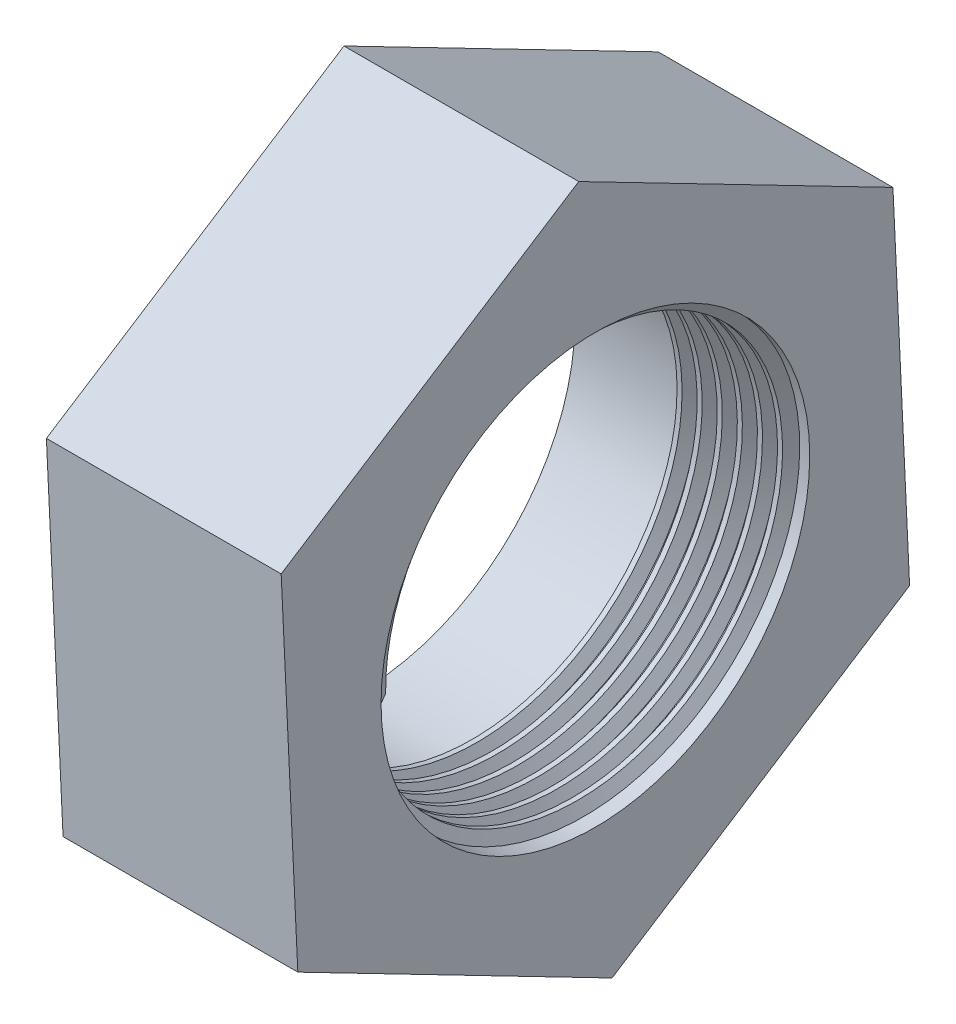
SolidWorks part; units mm, degrees
material "1060 Alloy"
ref_plane "Front Plane" through (0, 0, 0) normal (0, 0, 1) x (1, 0, 0)
ref_plane "Top Plane" through (0, 0, 0) normal (0, 1, 0) x (1, 0, 0)
ref_plane "Right Plane" through (0, 0, 0) normal (1, 0, 0) x (0, 0, -1)
sketch "Sketch1" plane through (0, 0, 0) normal (1, 0, 0) x (0, 0, -1)
  line L1 (7.8188, -4.0355) -> (7.4043, 4.7535)
  line L2 (7.4043, 4.7535) -> (-0.4145, 8.789)
  line L3 (-0.4145, 8.789) -> (-7.8188, 4.0355)
  line L4 (-7.8188, 4.0355) -> (-7.4043, -4.7535)
  line L5 (-7.4043, -4.7535) -> (0.4145, -8.789)
  line L6 (0.4145, -8.789) -> (7.8188, -4.0355)
  circle A0 centre (0, 0) radius 7.62 construction
  circle A1 centre (0, 0) radius 5.334
  dimension "D1" = 10.668
  dimension "D2" = 15.24
  dimension "D3" = 17.5781
extrude "Boss-Extrude1" add sketch "Sketch1" along normal blind 5.842
thread "Thread1" pitch 0.5 method extrude profile "Thread Profile1" start angle 0, offset 0, length 3.175, pitch 0.5, diameter 10.668
ref_plane "Plane1" through (5.842, 0, 5.334) normal (0, -1, 0) x (0, 0, 1)
sketch "Thread Profile1" plane through (5.842, 0, 5.334) normal (0, -1, 0) x (0, 0, 1)
  line L0 (0, 0) -> (0, 0.5) construction
  line L11 (0, 0) -> (0, 0.4375)
  line L12 (0, 0.4375) -> (-0.2706, 0.2812)
  line L13 (-0.2706, 0.2812) -> (-0.2706, 0.1562)
  line L15 (-0.2706, 0.1562) -> (0, 0)
  line L17 (-0.2706, 0.2187) -> (0, 0.2187) construction
  point P2 (0, 0)
  dimension "Pitch" = 0.5
  dimension "Profile_Angle" = 60
  dimension "Profile_Land" = 0.125
  dimension "Profile_Height" = 0.2706
equation "\"0.128i5\"=0.128"
